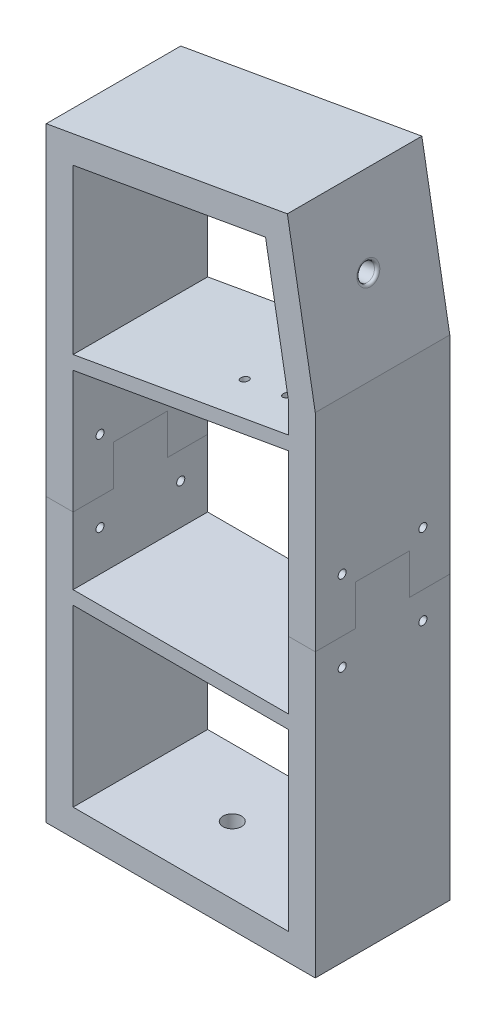
SolidWorks part; units mm, degrees
ref_plane "Front Plane" through (0, 0, 0) normal (0, 0, 1) x (1, 0, 0)
ref_plane "Top Plane" through (0, 0, 0) normal (0, 1, 0) x (1, 0, 0)
ref_plane "Right Plane" through (0, 0, 0) normal (1, 0, 0) x (0, 0, -1)
sketch "Sketch2" plane through (0, 0, 0) normal (0, 0, 1) x (1, 0, 0)
  line L6 (-50, 225.01) -> (-50, 0)
  line L8 (-50, 0) -> (50, 0)
  line L10 (-40, 216.619) -> (-40, 10)
  line L11 (-40, 10) -> (40, 10)
  line L12 (50, 0) -> (50, 182.01)
  line L13 (50, 182.01) -> (39.6312, 240.8144)
  line L14 (50, 182.01) -> (50, 266.0824) construction
  line L15 (39.6312, 240.8144) -> (-50, 225.01)
  line L16 (40, 10) -> (40, 181.1351)
  line L17 (40, 181.1351) -> (31.5196, 229.2298)
  line L18 (31.5196, 229.2298) -> (-40, 216.619)
  dimension "D1" = 182.01
  dimension "D2" = 100
  dimension "D3" = 10
  dimension "D4" = 225.01
  dimension "D6" = 10
extrude "Boss-Extrude1" add sketch "Sketch2" along normal blind 50
sketch "Sketch4" plane through (79.6179, 14.0388, 0) normal (0.9848, 0.1736, 0) x (0, 0, -1)
  line L0 (-25, 170.5625) -> (-25, 200.891) construction
  line L1 (-50, 170.5625) -> (0, 170.5625) construction
  line L2 (-50, 230.274) -> (0, 230.274) construction
  circle A0 centre (-25, 200.891) radius 3.2
  dimension "D1" = 6.4
  dimension "D2" = 29.383
extrude "Cut-Extrude1" cut sketch "Sketch4" against normal blind 10
sketch "Sketch7" plane through (0, 0, 50) normal (0, 0, 1) x (1, 0, 0)
  line L1 (40, 10) -> (40, 181.1351) construction
  line L5 (40, 169.7996) -> (40, 164.7224)
  line L7 (-40, 150.6163) -> (-40, 155.6934)
  line L10 (40, 169.7996) -> (-40, 155.6934)
  line L11 (-40, 150.6163) -> (40, 164.7224)
  line L12 (-40, 216.619) -> (-40, 10) construction
  line L13 (31.5196, 229.2298) -> (-40, 216.619) construction
  dimension "D1" = 60
  dimension "D3" = 5
extrude "Boss-Extrude2" add sketch "Sketch7" against normal blind 50
sketch "Sketch8" plane through (-50, 0, 0) normal (-1, 0, 0) x (0, 0, 1)
  line L0 (50, 225.01) -> (0, 225.01) construction
  line L1 (50, 225.01) -> (50, 0) construction
  line L3 (0, 225.01) -> (0, 0) construction
  line L4 (0, 204.1639) -> (50, 204.1639) construction
  circle A0 centre (25, 204.1639) radius 5
  dimension "D1" = 10
  dimension "D2" = 20.8461
extrude "Cut-Extrude3" cut sketch "Sketch8" against normal blind 10
sketch "Sketch9" plane through (128.3774, 180.3057, 0) normal (-0.1736, 0.9848, 0) x (-0.9848, -0.1736, 0)
  line L0 (76.8907, 25) -> (104.9692, 25) construction
  line L3 (104.9692, 34.6) -> (120.9692, 34.6) construction
  line L5 (76.8907, 50) -> (76.8907, 0) construction
  line L6 (104.9692, 25) -> (104.9692, 34.6) construction
  line L7 (104.9692, 25) -> (104.9692, 15.4) construction
  line L8 (120.9692, 34.6) -> (120.9692, 15.4) construction
  line L10 (120.9692, 15.4) -> (104.9692, 15.4) construction
  circle A0 centre (104.9692, 15.4) radius 1.485
  circle A1 centre (104.9692, 34.6) radius 1.485
  circle A2 centre (120.9692, 34.6) radius 1.485
  circle A3 centre (120.9692, 15.4) radius 1.485
  dimension "D1" = 28.0785
  dimension "D2" = 2.97
  dimension "D3" = 19.2
  dimension "D4" = 16
extrude "Cut-Extrude4" cut sketch "Sketch9" along normal up to next
sketch "Sketch10" plane through (0, 10, 0) normal (0, 1, 0) x (1, 0, 0)
  line L0 (50, -25) -> (24.131, -25) construction
  line L1 (-30.869, -50) -> (-30.869, 0) construction
  line L2 (50, -50) -> (50, 0) construction
  line L3 (-30, -25) -> (-5.8513, -25) construction
  circle A0 centre (-5.8513, -25) radius 3.425
  circle A1 centre (24.131, -25) radius 3.425
  dimension "D1" = 6.85
  dimension "D2" = 6.85
  dimension "D3" = 25.0177
  dimension "D4" = 55
extrude "Cut-Extrude5" cut sketch "Sketch10" against normal blind 10
sketch "Sketch11" plane through (0, 0, 50) normal (0, 0, 1) x (1, 0, 0)
  line L0 (-40, 75) -> (40, 75)
  line L3 (40, 75) -> (40, 80)
  line L4 (40, 80) -> (-40, 80)
  line L5 (-40, 80) -> (-40, 75)
  line L6 (-40, 150.6163) -> (-40, 10) construction
  line L7 (40, 10) -> (40, 164.7224) construction
  dimension "D1" = 5
  dimension "D2" = 75
extrude "Boss-Extrude3" add sketch "Sketch11" against normal blind 50
fillet "Fillet1" radius 1 1 edges at (44.1778, 215.0292, 25) type face fillet first side face at (34.3298, 213.2927, 25) second side face at (44.1778, 215.0292, 25)
sketch "Sketch13" plane through (-50, 0, 0) normal (-1, 0, 0) x (0, 0, 1)
  line L0 (0, 0) -> (0, 105) construction
  line L1 (50, 105) -> (50, 95) construction
  line L2 (0, 105) -> (15, 105)
  line L3 (15, 105) -> (15, 120)
  line L4 (15, 120) -> (35, 120)
  line L5 (35, 120) -> (35, 105)
  line L6 (35, 105) -> (50, 105)
  line L7 (50, 225.01) -> (50, 0) construction
  line L8 (50, 0) -> (0, 0) construction
  line L9 (0, 105) -> (0, 96.1035) construction
  line L10 (50, 95) -> (40, 95) construction
  line L11 (50, 105) -> (50, 125) construction
  line L12 (50, 125) -> (40, 125) construction
  line L13 (25, 120) -> (25, -15) construction
  circle A0 centre (40, 125) radius 1.5
  circle A1 centre (40, 95) radius 1.5
  circle A4 centre (10, 95) radius 1.5
  circle A5 centre (10, 125) radius 1.5
  point P25 (0, 0)
  dimension "D6" = 3
  dimension "D7" = 3
  dimension "D1" = 15
  dimension "D2" = 35
  dimension "D3" = 15
  dimension "D4" = 120
  dimension "D5" = 105
extrude "Cut-Extrude6" cut sketch "Sketch13" against normal through all contours A4 | A5 | A0 | A1
sketch "Sketch14" plane through (-50, 0, 0) normal (-1, 0, 0) x (0, 0, 1)
  line L0 (50, 0) -> (50, 105) construction
  line L1 (50, 225.01) -> (50, 0) construction
  line L2 (50, 105) -> (35, 105)
  line L3 (35, 105) -> (35, 120)
  line L4 (35, 120) -> (15, 120)
  line L5 (15, 120) -> (15, 105)
  line L6 (15, 105) -> (0, 105)
  line L7 (0, 225.01) -> (0, 0) construction
  line L8 (50, 0) -> (0, 0) construction
  dimension "D1" = 15
  dimension "D2" = 35
  dimension "D3" = 15
  dimension "D4" = 120
  dimension "D5" = 105
split "Split1" trim tools "Sketch14" bodies to split 113 resulting bodies 114 115
